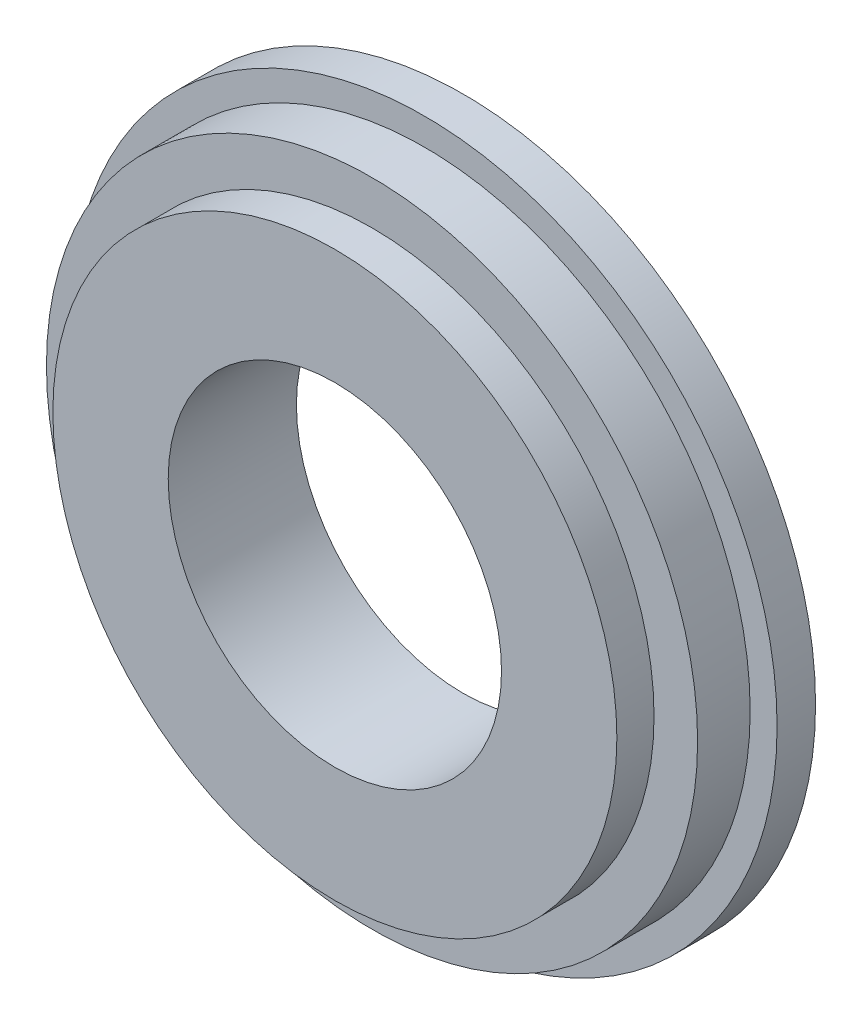
SolidWorks part; units mm, degrees
ref_plane "前视基准面" through (0, 0, 0) normal (0, 0, 1) x (1, 0, 0)
ref_plane "上视基准面" through (0, 0, 0) normal (0, 1, 0) x (1, 0, 0)
ref_plane "右视基准面" through (0, 0, 0) normal (1, 0, 0) x (0, 0, -1)
sketch "草图1" plane through (0, 0, 0) normal (0, 0, 1) x (1, 0, 0)
  circle A0 centre (0, 0) radius 22
  circle A1 centre (0, 0) radius 25.4
  circle A2 centre (0, 0) radius 27.5
  circle A3 centre (0, 0) radius 13
  dimension "D1" = 55
  dimension "D2" = 50.8
  dimension "D3" = 44
  dimension "D4" = 26
extrude "凸台-拉伸1" add sketch "草图1" along normal blind 3 contours A2
extrude "凸台-拉伸2" add sketch "草图1<3>" along normal blind 7.1 contours A1
sketch "草图1<3>" plane through (0, 0, 0) normal (0, 0, 1) x (1, 0, 0) same geometry as "草图1"
extrude "凸台-拉伸3" add sketch "草图1<4>" along normal blind 10 contours A0
sketch "草图1<4>" plane through (0, 0, 0) normal (0, 0, 1) x (1, 0, 0) same geometry as "草图1"
extrude "切除-拉伸1" cut sketch "草图1<5>" along normal blind 10 contours A3 region at (0, 0, 0)
sketch "草图1<5>" plane through (0, 0, 0) normal (0, 0, 1) x (1, 0, 0) same geometry as "草图1"
